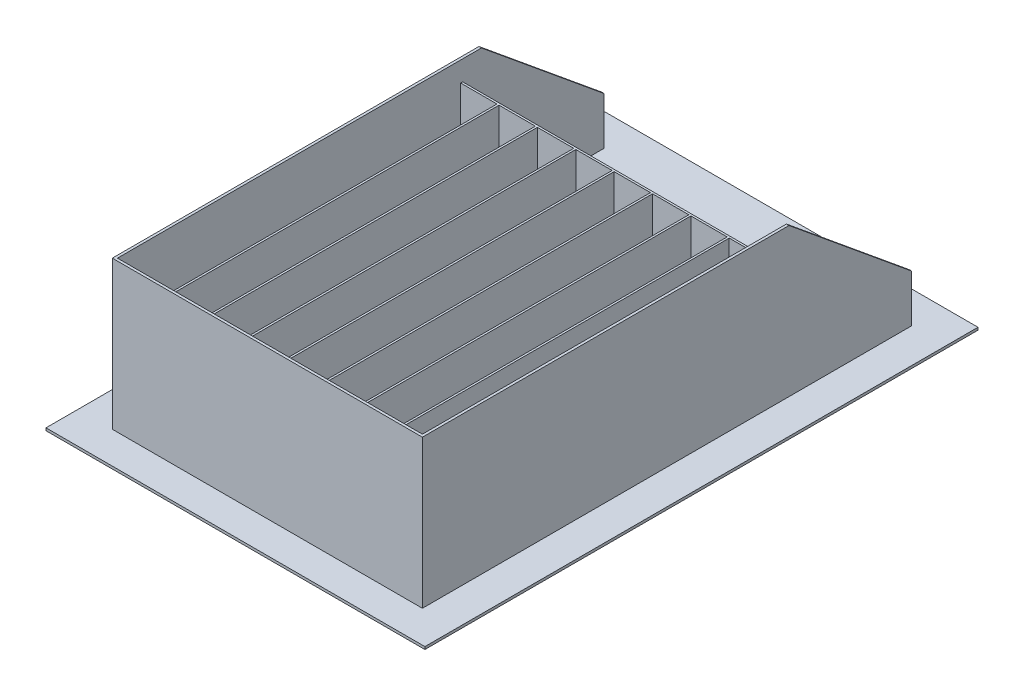
SolidWorks part; units mm, degrees
material "6061-T6 (SS)"
ref_plane "Front Plane" through (0, 0, 0) normal (0, 0, 1) x (1, 0, 0)
ref_plane "Top Plane" through (0, 0, 0) normal (0, 1, 0) x (1, 0, 0)
ref_plane "Right Plane" through (0, 0, 0) normal (1, 0, 0) x (0, 0, -1)
sketch "Sketch1" plane through (0, 0, 0) normal (0, 1, 0) x (1, 0, 0)
  line L1 (0, 0) -> (45.6, 0)
  line L2 (0, 0) -> (0, 430.25)
  line L3 (0, 430.25) -> (45.6, 430.25)
  line L4 (382.3, 0) -> (382.3, 430.25)
  line L5 (385.5, -3.2) -> (385.5, 432.75)
  line L6 (-3.2, -3.2) -> (385.5, -3.2)
  line L7 (-3.2, -3.2) -> (-3.2, 432.75)
  line L8 (-3.2, 433.45) -> (385.5, 433.45) construction
  line L9 (-3.2, 432.75) -> (385.5, 432.75)
  line L10 (45.6, 430.25) -> (45.6, 0)
  line L11 (-3.2, -3.2) -> (-3.2, 433.45) construction
  line L12 (385.5, -3.2) -> (385.5, 433.45) construction
  line L13 (48.1, 0) -> (48.1, 430.25)
  line L14 (48.1, 430.25) -> (93.7, 430.25)
  line L15 (48.1, 0) -> (93.7, 0)
  line L16 (0, 430.25) -> (382.3, 430.25) construction
  line L17 (93.7, 430.25) -> (93.7, 0)
  line L18 (0, 0) -> (382.3, 0) construction
  line L19 (96.2, 0) -> (96.2, 430.25)
  line L20 (141.8, 430.25) -> (141.8, 0)
  line L21 (144.3, 0) -> (144.3, 430.25)
  line L22 (189.9, 430.25) -> (189.9, 0)
  line L23 (192.4, 0) -> (192.4, 430.25)
  line L24 (238, 430.25) -> (238, 0)
  line L25 (240.5, 0) -> (240.5, 430.25)
  line L26 (286.1, 430.25) -> (286.1, 0)
  line L27 (288.6, 0) -> (288.6, 430.25)
  line L28 (334.2, 430.25) -> (334.2, 0)
  line L29 (336.7, 0) -> (336.7, 430.25)
  line L30 (96.2, 430.25) -> (141.8, 430.25)
  line L31 (144.3, 430.25) -> (189.9, 430.25)
  line L32 (96.2, 0) -> (141.8, 0)
  line L33 (144.3, 0) -> (189.9, 0)
  line L34 (192.4, 0) -> (238, 0)
  line L35 (240.5, 0) -> (286.1, 0)
  line L36 (288.6, 0) -> (334.2, 0)
  line L37 (336.7, 0) -> (382.3, 0)
  line L38 (192.4, 430.25) -> (238, 430.25)
  line L39 (240.5, 430.25) -> (286.1, 430.25)
  line L40 (288.6, 430.25) -> (334.2, 430.25)
  line L41 (336.7, 430.25) -> (382.3, 430.25)
  dimension "D1" = 430.25
  dimension "D2" = 382.3
  dimension "D4" = 2.5
  dimension "D3" = 3.2
  dimension "D5" = 2.5
  dimension "D6" = 45.6
  dimension "D8" = 45.6
  dimension "D7" = 7
extrude "Boss-Extrude1" add sketch "Sketch1" along normal blind 189
sketch "Sketch2" plane through (0, 0, 3.2) normal (0, 0, 1) x (1, 0, 0)
  line L0 (385.5, 189) -> (385.5, 0) construction
  line L1 (-3.2, 0) -> (385.5, 0)
  line L2 (-3.2, 0) -> (-3.2, 3.2)
  line L3 (-3.2, 3.2) -> (385.5, 3.2)
  line L4 (385.5, 0) -> (385.5, 3.2)
  dimension "D1" = 3.2
extrude "Boss-Extrude2" add sketch "Sketch2" against normal through all
sketch "Sketch3" plane through (0, 189, 0) normal (0, 1, 0) x (1, 0, 0)
  line L0 (0, 430.25) -> (0, 432.75)
  line L1 (385.5, 432.75) -> (-3.2, 432.75) construction
  line L2 (0, 432.75) -> (382.3, 432.75)
  line L3 (382.3, 430.25) -> (382.3, 432.75)
  line L4 (382.3, 430.25) -> (336.7, 430.25)
  line L5 (336.7, 430.25) -> (336.7, 0)
  line L6 (336.7, 0) -> (334.2, 0)
  line L7 (334.2, 0) -> (334.2, 430.25) construction
  line L8 (334.2, 0) -> (334.2, 430.25) construction
  line L9 (334.2, 0) -> (334.2, 430.25)
  line L10 (334.2, 430.25) -> (288.6, 430.25)
  line L11 (288.6, 430.25) -> (288.6, 0)
  line L12 (288.6, 0) -> (286.1, 0)
  line L13 (286.1, 0) -> (286.1, 430.25)
  line L14 (286.1, 430.25) -> (240.5, 430.25)
  line L15 (240.5, 430.25) -> (240.5, 0)
  line L16 (240.5, 0) -> (238, 0)
  line L17 (238, 0) -> (238, 430.25)
  line L18 (238, 430.25) -> (192.4, 430.25)
  line L19 (192.4, 430.25) -> (192.4, 0)
  line L20 (192.4, 0) -> (189.9, 0)
  line L21 (189.9, 0) -> (189.9, 430.25)
  line L22 (189.9, 430.25) -> (144.3, 430.25)
  line L23 (144.3, 430.25) -> (144.3, 0)
  line L24 (144.3, 0) -> (141.8, 0)
  line L25 (141.8, 0) -> (141.8, 430.25)
  line L26 (141.8, 430.25) -> (96.2, 430.25)
  line L27 (96.2, 430.25) -> (96.2, 0)
  line L28 (96.2, 0) -> (93.7, 0)
  line L29 (93.7, 0) -> (93.7, 430.25)
  line L30 (93.7, 430.25) -> (48.1, 430.25)
  line L31 (48.1, 430.25) -> (48.1, 0)
  line L32 (48.1, 0) -> (45.6, 0)
  line L33 (45.6, 0) -> (45.6, 430.25)
  line L34 (45.6, 430.25) -> (0, 430.25)
extrude "Cut-Extrude1" cut sketch "Sketch3" against normal blind 25
sketch "Sketch4" plane through (385.5, 0, 0) normal (1, 0, 0) x (0, 0, -1)
  line L0 (432.75, 189) -> (662.75, 0)
  line L1 (432.75, 0) -> (662.75, 0)
  line L2 (432.75, 0) -> (432.75, 189)
  dimension "D1" = 230
extrude "Boss-Extrude4" add sketch "Sketch4" against normal blind 3.2 contours L0 L1 L2
sketch "Sketch7" plane through (-3.2, 0, 0) normal (-1, 0, 0) x (0, 0, 1)
  line L0 (-432.75, 164) -> (-432.75, 189)
  line L8 (-430.25, 3.2) -> (0, 3.2)
  line L9 (0, 3.2) -> (0, 189)
  line L10 (0, 189) -> (-432.75, 189)
  line L11 (-432.75, 189) -> (-662.75, 0)
  line L12 (-662.75, 0) -> (-432.75, 0)
  line L13 (-432.75, 0) -> (-432.75, 164)
  line L14 (-432.75, 164) -> (-430.25, 164)
  line L15 (-430.25, 164) -> (-430.25, 3.2)
  line L19 (-432.75, 189) -> (-662.75, 0)
  line L20 (-662.75, 0) -> (-432.75, 0)
  line L21 (-432.75, 0) -> (-432.75, 164)
  dimension "D1" = 0
extrude "Boss-Extrude5" add sketch "Sketch7" against normal blind 3.2
sketch "Sketch9" plane through (0, 0, 0) normal (1, 0, 0) x (0, 0, -1)
  line L0 (662.75, 0) -> (658.8558, 3.2)
  line L1 (432.75, 0) -> (662.75, 0)
  line L2 (432.75, 0) -> (432.75, 3.2)
  line L3 (432.75, 3.2) -> (658.8558, 3.2)
  line L5 (432.75, 189) -> (662.75, 0) construction
  line L6 (662.75, 0) -> (432.75, 0) construction
  dimension "D1" = 3.2
extrude "Boss-Extrude6" add sketch "Sketch9" along normal up to next
sketch "Sketch11" plane through (385.5, 0, 0) normal (1, 0, 0) x (0, 0, -1)
  line L1 (662.75, 0) -> (610.16, 0)
  line L2 (662.75, 0) -> (662.75, 168.0196)
  line L3 (662.75, 168.0196) -> (610.16, 168.0196)
  line L4 (610.16, 0) -> (610.16, 168.0196)
  dimension "D1" = 52.59
extrude "Cut-Extrude2" cut sketch "Sketch11" against normal up to next
sketch "Sketch12" plane through (385.5, 0, 0) normal (1, 0, 0) x (0, 0, -1)
  line L1 (432.75, 189) -> (610.16, 43.2153) construction
  line L2 (442.2732, 200.5891) -> (619.6832, 54.8044)
  line L3 (456.3764, 189) -> (610.16, 62.63)
  line L4 (432.75, 189) -> (610.16, 43.2153)
  line L5 (432.75, 189) -> (456.3764, 189)
  line L6 (610.16, 43.2153) -> (610.16, 62.63)
  dimension "D1" = 15
extrude "Boss-Extrude7" add sketch "Sketch12" against normal blind 3.2
sketch "Sketch13" plane through (-3.2, 0, 0) normal (-1, 0, 0) x (0, 0, 1)
  line L0 (-610.16, 62.63) -> (-610.16, 3.2) construction
  line L1 (-432.75, 189) -> (-610.16, 43.2153) construction
  line L2 (0, 189) -> (-456.3764, 189) construction
  line L3 (-610.16, 62.63) -> (-456.3764, 189) construction
  line L4 (-610.16, 62.63) -> (-610.16, 43.2153)
  line L5 (-432.75, 189) -> (-610.16, 43.2153)
  line L6 (-432.75, 189) -> (-456.3764, 189)
  line L7 (-610.16, 62.63) -> (-456.3764, 189)
extrude "Boss-Extrude8" add sketch "Sketch13" against normal blind 3.2
sketch "Sketch14" plane through (0, 0, -610.16) normal (0, 0, -1) x (-1, 0, 0)
  line L0 (0, 3.2) -> (3.2, 3.2) construction
  line L1 (3.2, 0) -> (3.2, 62.63) construction
  line L2 (-382.3, 3.2) -> (-385.5, 3.2) construction
  line L3 (-385.5, 62.63) -> (-385.5, 0) construction
  line L5 (-385.5, 3.2) -> (3.2, 3.2)
  line L6 (-385.5, 3.2) -> (-385.5, 0)
  line L7 (-385.5, 0) -> (3.2, 0)
  line L8 (3.2, 3.2) -> (3.2, 0)
extrude "Boss-Extrude9" add sketch "Sketch14" along normal blind 40
sketch "Sketch15" plane through (0, 0, 3.2) normal (0, 0, 1) x (1, 0, 0)
  line L0 (385.5, 189) -> (385.5, 0) construction
  line L1 (-3.2, 0) -> (385.5, 0)
  line L2 (-3.2, 0) -> (-3.2, 3.2)
  line L3 (-3.2, 3.2) -> (385.5, 3.2)
  line L4 (385.5, 0) -> (385.5, 3.2)
  dimension "D1" = 3.2
extrude "Boss-Extrude10" add sketch "Sketch15" along normal blind 40
sketch "Sketch16" plane through (385.5, 0, 0) normal (1, 0, 0) x (0, 0, -1)
  line L1 (-43.2, 3.2) -> (650.16, 3.2)
  line L2 (-43.2, 3.2) -> (-43.2, 0)
  line L3 (-43.2, 0) -> (650.16, 0)
  line L4 (650.16, 3.2) -> (650.16, 0)
extrude "Boss-Extrude11" add sketch "Sketch16" along normal blind 43.15
sketch "Sketch17" plane through (-3.2, 0, 0) normal (-1, 0, 0) x (0, 0, 1)
  line L1 (-650.16, 3.2) -> (43.2, 3.2)
  line L2 (-650.16, 3.2) -> (-650.16, 0)
  line L3 (-650.16, 0) -> (43.2, 0)
  line L4 (43.2, 3.2) -> (43.2, 0)
extrude "Boss-Extrude12" add sketch "Sketch17" along normal blind 43.15
